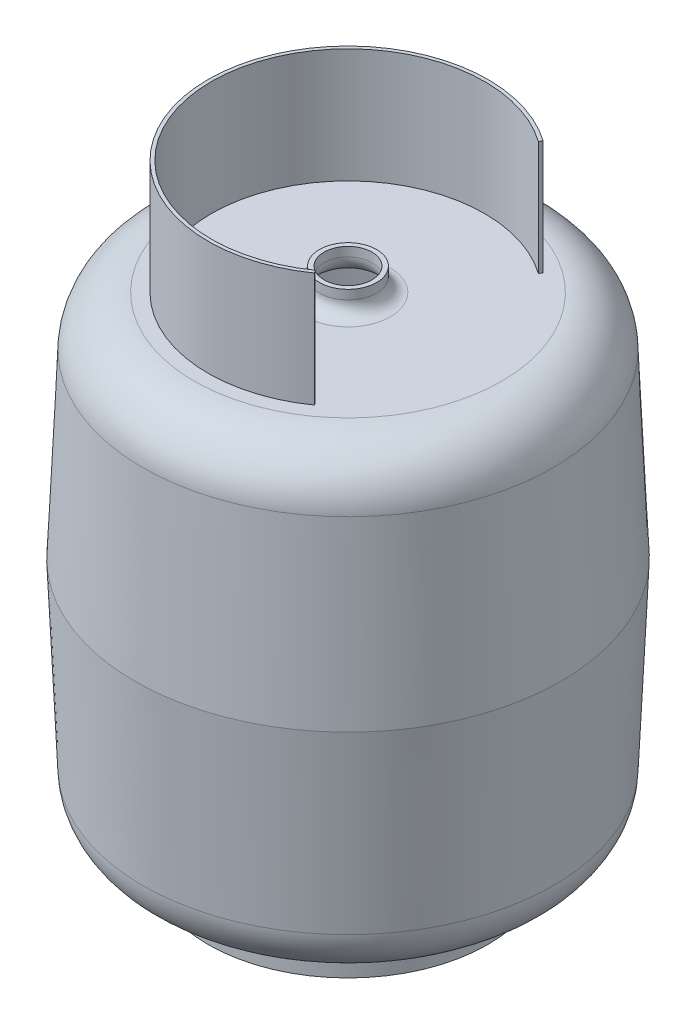
SolidWorks part; units mm, degrees
material "1060 Alloy"
ref_plane "Front Plane" through (0, 0, 0) normal (0, 0, 1) x (1, 0, 0)
ref_plane "Top Plane" through (0, 0, 0) normal (0, 1, 0) x (1, 0, 0)
ref_plane "Right Plane" through (0, 0, 0) normal (1, 0, 0) x (0, 0, -1)
sketch "Sketch1" plane through (0, 0, 0) normal (0, 0, 1) x (1, 0, 0)
  line L0 (0, 0) -> (0, -402.5)
  line L1 (0, -402.5) -> (134.4219, -402.5)
  line L2 (179.379, -359.4629) -> (186.2868, -201.25)
  line L3 (186.2868, -201.25) -> (179.379, -43.0371)
  line L4 (134.4219, 0) -> (37, 0)
  line L5 (25, 12) -> (25, 20)
  line L6 (25, 20) -> (0, 20)
  line L7 (0, 20) -> (0, 0)
  arc A0 (179.379, -43.0371) -> (134.4219, 0) centre (134.4219, -45) ccw
  arc A1 (134.4219, -402.5) -> (179.379, -359.4629) centre (134.4219, -357.5) ccw
  arc A2 (37, 0) -> (25, 12) centre (37, 12) cw
  point P11 (177.5, 0)
  point P14 (177.5, -402.5)
  point P17 (25, 0)
  dimension "D8" = 45
  dimension "D9" = 12
  dimension "D1" = 177.5
  dimension "D2" = 92.5
  dimension "D3" = 92.5
  dimension "D4" = 402.5
  dimension "D5" = 25
  dimension "D6" = 201.25
  dimension "D7" = 20
revolve "Revolve1" add sketch "Sketch1" angle 360 about L0
shell "Shell1" thickness 4 removed face at (-25, 20, 0)
sketch "Sketch2" plane through (0, 0, 0) normal (0, 1, 0) x (1, 0, 0)
  line L0 (0, 0) -> (134.4219, 0) construction
  line L1 (68.8889, 97.5495) -> (70.6195, 100)
  line L2 (68.8889, -97.5495) -> (70.6195, -100)
  arc A1 (68.8889, 97.5495) -> (68.8889, -97.5495) centre (0, 0) ccw
  arc A2 (70.6195, 100) -> (70.6195, -100) centre (0, 0) ccw
  circle A4 centre (0, 0) radius 134.4219 construction
  dimension "D1" = 12
  dimension "D4" = 3
  dimension "D2" = 100
  dimension "D3" = 100
extrude "Boss-Extrude1" add sketch "Sketch2" along normal blind 100
sketch "Sketch3" plane through (0, -402.5, 0) normal (0, -1, 0) x (1, 0, 0)
  circle A0 centre (0, 0) radius 122.4219
  circle A1 centre (0, 0) radius 134.4219 construction
  circle A2 centre (0, 0) radius 119.4219
  dimension "D1" = 12
  dimension "D2" = 3
extrude "Boss-Extrude2" add sketch "Sketch3" along normal blind 30
